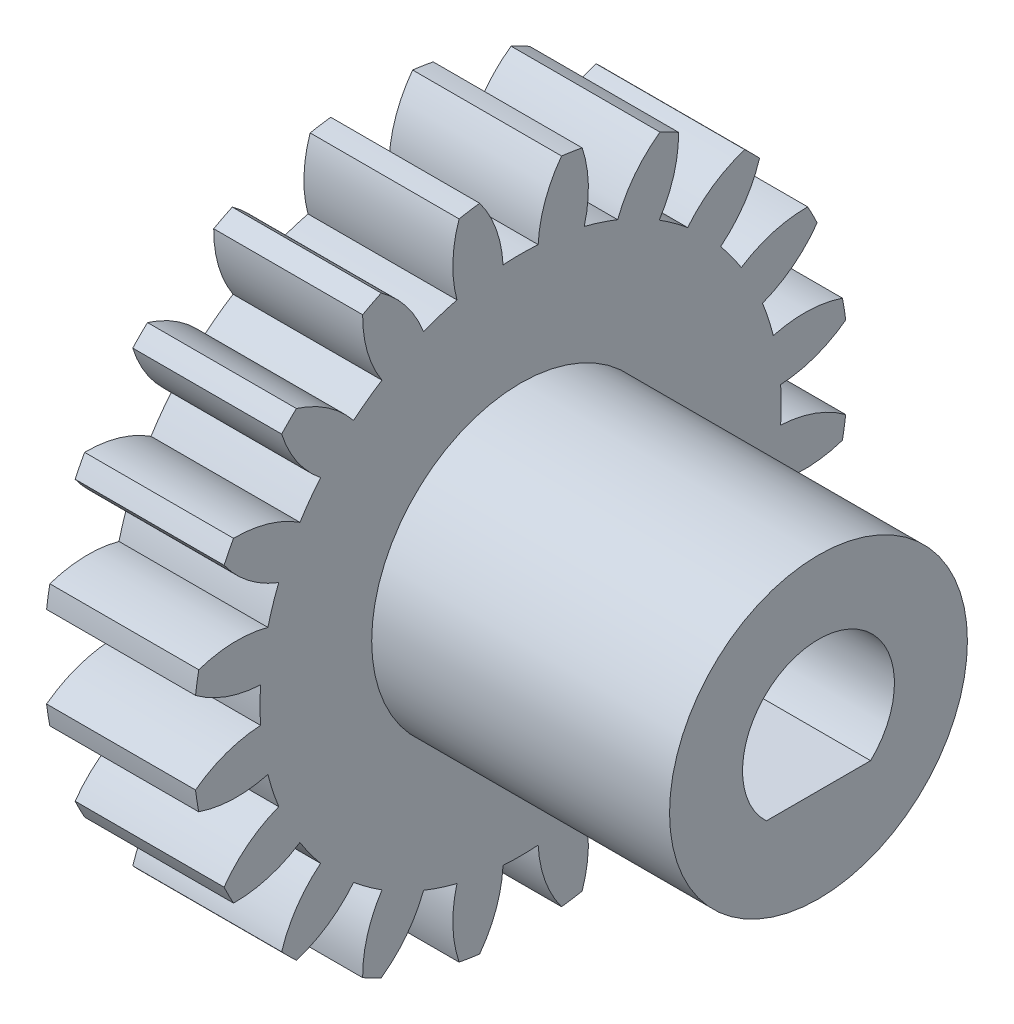
SolidWorks part; units mm, degrees
ref_plane "Plane1" through (0, 0, 0) normal (0, 0, 1) x (1, 0, 0)
ref_plane "Plane2" through (0, 0, 0) normal (0, 1, 0) x (1, 0, 0)
ref_plane "Plane3" through (0, 0, 0) normal (1, 0, 0) x (0, 0, -1)
sketch "HoldingSke" plane through (0, 0, 0) normal (0, 1, 0) x (1, 0, 0)
  line L0 (0, 0) -> (0.9397, -0.342)
  line L1 (-15, 0) -> (100, 0) construction
  line L2 (0, 0) -> (-2.1039, 2.3779)
  line L3 (0, 0) -> (-11.863, 4.5341)
  line L4 (0, 0) -> (8.1152, 2.9537)
  line L5 (0, 0) -> (-46.8476, -17.4728)
  line L6 (0, 0) -> (-4.1448, -2.7965)
  line L7 (-2.1039, 2.3779) -> (8.6586, 51.2059)
  line L8 (-76.2, 54.61) -> (-75.3, 54.61)
  line L9 (-67.7845, 28.3722) -> (-49.3413, 33.142)
  line L10 (-76.2, 71.12) -> (104.1128, 71.12)
  line L11 (0, 0) -> (-5, 0)
  line L12 (-76.2, 101.6) -> (-76.162, 101.6)
  line L13 (24.9733, 27.94) -> (52.9518, 28.4284)
  line L14 (24.9733, 27.94) -> (24.9743, 27.94)
  line L15 (24.9733, 27.94) -> (100.4006, 29.5858)
  line L16 (-63.627, -1) -> (-12.827, -1)
  circle A0 centre (0, 0) radius 2.5
  circle A1 centre (0, 0) radius 8.749
  circle A2 centre (0, 0) radius 37.5
  circle A3 centre (0, 0) radius 2.5
  dimension "Num_teeth" = 20
  dimension "Pitch_radius" = 180.3128
  dimension "Width" = 5
  dimension "Thickness" = 5
sketch "BasProSke" plane through (0, 0, 0) normal (0, 1, 0) x (1, 0, 0)
  line L0 (-10, 0) -> (60, 0) construction
  line L1 (0, 0) -> (0, 11)
  line L2 (0, 0) -> (5, 0)
  line L3 (5, 0) -> (5, 11)
  line L4 (5, 11) -> (0, 11)
  dimension "Thickness" = 5
  dimension "Diameter" = 22
revolve "Base-Revolve" add sketch "BasProSke" angle 360 about L0
sketch "TooCutSke" plane through (0, 0, 0) normal (1, 0, 0) x (0, 0, -1)
  line L1 (0, 0) -> (0, 107) construction
  line L2 (0, 0) -> (-0.8511, 9.9637) construction
  line L3 (0, 0) -> (-3.1206, 19.7028) construction
  line L4 (-0.8511, 9.9637) -> (-1.5603, 9.8514) construction
  arc A0 (0.5894, 8.7291) -> (-0.5894, 8.7291) centre (0, 0) ccw
  arc A1 (1.3917, 10.9372) -> (-1.3917, 10.9372) centre (0, 0) ccw
  circle A2 centre (0, 0) radius 10 construction
  circle A3 centre (0, 0) radius 9.6815 construction
  arc A4 (-0.5894, 8.7291) -> (-1.3917, 10.9372) centre (-4.5843, 8.5273) ccw
  arc A5 (1.3917, 10.9372) -> (0.5894, 8.7291) centre (4.5843, 8.5273) ccw
extrude "ToothCut" cut sketch "TooCutSke" along normal through all
fillet "Breaks" [suppressed] radius 0.02 tangent propagation no
fillet "RootFillets" [suppressed] radius 0.251
pattern_circular "TeethCuts" count 20 every 18 about axis through (-10, 0, 0) along (1, 0, 0) of "ToothCut", "RootFillets", "Breaks"
sketch "HubNeaOneSke" plane through (0, 0, 0) normal (-1, 0, 0) x (0, 0, 1)
  circle A0 centre (0, 0) radius 8.749
  dimension "Diameter" = 17.498
extrude "HubNearOne" [suppressed] add sketch "HubNeaOneSke" along normal blind 45.0001
sketch "HubNeaBotSke" plane through (0, 0, 0) normal (-1, 0, 0) x (0, 0, 1)
  circle A0 centre (0, 0) radius 8.749
  dimension "Diameter" = 17.498
extrude "HubNearBoth" [suppressed] add sketch "HubNeaBotSke" along normal blind 22.5
ref_plane "FarPln" through (5, 0, 0) normal (1, 0, 0) x (0, 0, -1)
sketch "HubFarSke" plane through (5, 0, 0) normal (1, 0, 0) x (0, 0, -1)
  circle A0 centre (0, 0) radius 8.749
  dimension "Diameter" = 17.498
extrude "HubFar" [suppressed] add sketch "HubFarSke" along normal blind 22.5
sketch "BorSke" plane through (0, 0, 0) normal (1, 0, 0) x (0, 0, -1)
  circle A0 centre (0, 0) radius 2.5
  dimension "Diameter" = 5
extrude "Bore" cut sketch "BorSke" along normal mid plane 100.0001
sketch "KeySke" plane through (0, 0, 0) normal (1, 0, 0) x (0, 0, -1)
  line L0 (-1, 0) -> (-1, 3.4)
  line L1 (-1, 3.4) -> (1, 3.4)
  line L2 (1, 3.4) -> (1, 0)
  line L3 (0, 0) -> (0, 34) construction
  line L4 (-1, 0) -> (1, 0)
  dimension "Width" = 2
extrude "Keyway" [suppressed] cut sketch "KeySke" along normal mid plane 100.0001
pattern_circular "Keyway2" [suppressed] count 2 every 90 about axis through (-10, 0, 0) along (1, 0, 0) reverse direction yes
sketch "Sketch1" plane through (5, 0, 0) normal (1, 0, 0) x (0, 0, -1)
  circle A0 centre (0, 0) radius 5
  dimension "D1" = 10
extrude "Boss-Extrude2" add sketch "Sketch1" along normal blind 10 and the other way through all
sketch "Sketch2" plane through (15, 0, 0) normal (1, 0, 0) x (0, 0, -1)
  line L0 (-1.75, -1.8547) -> (1.75, -1.8547)
  circle A0 centre (0, 0) radius 2.55
  dimension "D1" = 5.1
  dimension "D2" = 3.5
extrude "Cut-Extrude1" cut sketch "Sketch2" against normal through all contours L0 A0 region at (15, 0.1905, 0)
equation "' \"Module@HoldingSke\" = 6.35"
equation "' \"Num_teeth@HoldingSke\" = 12"
equation "' \"Ap@HoldingSke\" =  20"
equation "' \"Ap@HoldingSke\" = 20"
equation "' \"Width@HoldingSke\" = 0.5 * 25.4"
equation "' \"Hub_dia@HoldingSke\"= 1 * 25.4"
equation "' \"Hub_dia@HoldingSke\" = 1 * 25.4"
equation "' \"Overall_len@HoldingSke\" = 1.0 * 25.4"
equation "' \"Bore@HoldingSke\" = 0.75 * 25.4"
equation "' \"T_dim@HoldingSke\" = 0.1 * 25.4"
equation "' \"Width@KeySke\" = 0.25 * 25.4"
equation "' \"Show_teeth@HoldingSke\" = 13"
equation "' \"Backlash@HoldingSke\" = 0.009 * 25.4"
equation "' \"Addendum_fac@HoldingSke\" = 1.0"
equation "' \"Dedendum_fac@HoldingSke\" = 1.25"
equation "' \"Dedendum_add@HoldingSke\" = 0.00005 * 25.4"
equation "' \"Clearance_fac@HoldingSke\" = 0.25"
equation "\"Pitch@HoldingSke\" = 1 / \"Module@HoldingSke\""
equation "\"Overcut_dia@TooCutSke\" = (\"Num_teeth@HoldingSke\" + 2 * \"Addendum_fac@HoldingSke\") / \"Pitch@HoldingSke\" + 0.002 * 25.4"
equation "\"Pitch_dia@TooCutSke\" = \"Num_teeth@HoldingSke\" / \"Pitch@HoldingSke\""
equation "\"Base_dia@TooCutSke\" = \"Num_teeth@HoldingSke\" / \"Pitch@HoldingSke\" * cos((\"Ap@HoldingSke\"  * 3.14159265 / 180))"
equation "\"Root_dia@TooCutSke\" = (\"Num_teeth@HoldingSke\" + 2) / \"Pitch@HoldingSke\" - 2 * (\"Addendum_fac@HoldingSke\" + \"Dedendum_fac@HoldingSke\") / \"Pitch@HoldingSke\" - \"Dedendum_add@HoldingSke\" * 2"
equation "\"Half_ang@TooCutSke\" = 180 / \"Num_teeth@HoldingSke\""
equation "\"Half_CT@TooCutSke\" = \"Num_teeth@HoldingSke\" / \"Pitch@HoldingSke\" * sin((3.14159265 / 2 / \"Num_teeth@HoldingSke\")) / 2 - 7 * \"Backlash@HoldingSke\" / 4"
equation "\"Flank_rad@TooCutSke\" = \"Num_teeth@HoldingSke\" / \"Pitch@HoldingSke\" / 5"
equation "\"Radius@RootFillets\" = \"Clearance_fac@HoldingSke\" / \"Pitch@HoldingSke\" + \"Dedendum_add@HoldingSke\""
equation "\"Break_rad@Breaks\" = 0.02 / \"Pitch@HoldingSke\""
equation "\"Thickness@HoldingSke\" = \"Width@HoldingSke\""
equation "\"OAL@HoldingSke\" = \"Thickness@HoldingSke\""
equation "\"MHD@HoldingSke\" = (\"Num_teeth@HoldingSke\" + 2) / \"Pitch@HoldingSke\" - 2 * (\"Addendum_fac@HoldingSke\" + \"Dedendum_fac@HoldingSke\")  / \"Pitch@HoldingSke\" - \"Dedendum_add@HoldingSke\" * 2"
equation "\"MBD@HoldingSke\" = (\"Num_teeth@HoldingSke\" + 2) / \"Pitch@HoldingSke\" - 2 * (\"Addendum_fac@HoldingSke\" + \"Dedendum_fac@HoldingSke\")  / \"Pitch@HoldingSke\" - \"Dedendum_add@HoldingSke\" * 2 - 0.002 * 25.4"
equation "\"MHD@HoldingSke\" = ((sgn( \"MHD@HoldingSke\" - \"Hub_dia@HoldingSke\" )-1)*( \"MHD@HoldingSke\" - \"Hub_dia@HoldingSke\" ))/-2+ \"Hub_dia@HoldingSke\""
equation "\"MBD@HoldingSke\" = ((sgn( \"MBD@HoldingSke\" - \"Bore@HoldingSke\" )-1)*( \"MBD@HoldingSke\" - \"Bore@HoldingSke\" ))/-2+ \"Bore@HoldingSke\""
equation "\"OAL@HoldingSke\" = ((sgn( \"OAL@HoldingSke\" - \"Overall_len@HoldingSke\" )+1)*( \"OAL@HoldingSke\" - \"Overall_len@HoldingSke\" ))/2 + \"Overall_len@HoldingSke\" + 0.000002 * 25.4"
equation "\"Num_teeth@TeethCuts\" = int( \"Show_teeth@HoldingSke\" ) + 1"
equation "\"Num_teeth@TeethCuts\" = ((sgn( \"Num_teeth@TeethCuts\" - \"Num_teeth@HoldingSke\" )-1)*( \"Num_teeth@TeethCuts\" - \"Num_teeth@HoldingSke\" ))/-2+ \"Num_teeth@HoldingSke\""
equation "\"Num_teeth@TeethCuts\" = ((sgn( \"Num_teeth@TeethCuts\" - 2.0)+1)*( \"Num_teeth@TeethCuts\" - 2.0))/2 +2.0"
equation "\"Angle@TeethCuts\" = 360.0 / \"Num_teeth@HoldingSke\""
equation "\"Diameter@BasProSke\" = (\"Num_teeth@HoldingSke\" + 2 * \"Addendum_fac@HoldingSke\") / \"Pitch@HoldingSke\""
equation "\"Thickness@BasProSke\"  = \"Thickness@HoldingSke\""
equation "' \"Fillet_rad@BasProSke\" =  \"Thickness@HoldingSke\" * 0.05"
equation "' \"Fillet_rad@BasProSke\" = \"Thickness@HoldingSke\" * 0.05"
equation "\"MHD@HoldingSke\" = ((sgn( \"MHD@HoldingSke\" - \"Root_dia@TooCutSke\" )-1)*( \"MHD@HoldingSke\" - \"Root_dia@TooCutSke\" ))/-2+ \"Root_dia@TooCutSke\""
equation "\"Diameter@HubNeaOneSke\" = \"MHD@HoldingSke\""
equation "\"Length@HubNearOne\" = \"OAL@HoldingSke\" - \"Thickness@BasProSke\""
equation "\"Diameter@HubNeaBotSke\" = \"MHD@HoldingSke\""
equation "\"Length@HubNearBoth\" = ( \"OAL@HoldingSke\" - \"Thickness@BasProSke\" ) / 2.0"
equation "\"Thickness@FarPln\" = \"Thickness@BasProSke\""
equation "\"Diameter@HubFarSke\" = \"MHD@HoldingSke\""
equation "\"Length@HubFar\" = ( \"OAL@HoldingSke\" - \"Thickness@BasProSke\" ) / 2.0"
equation "\"Diameter@BorSke\" = \"MBD@HoldingSke\""
equation "\"D1@Bore\" = \"OAL@HoldingSke\" * 2.0"
equation "\"D1@Keyway\" = \"OAL@HoldingSke\" * 2.0"
equation "\"Offset@KeySke\" = \"T_dim@HoldingSke\" + \"MBD@HoldingSke\" / 2.0"
